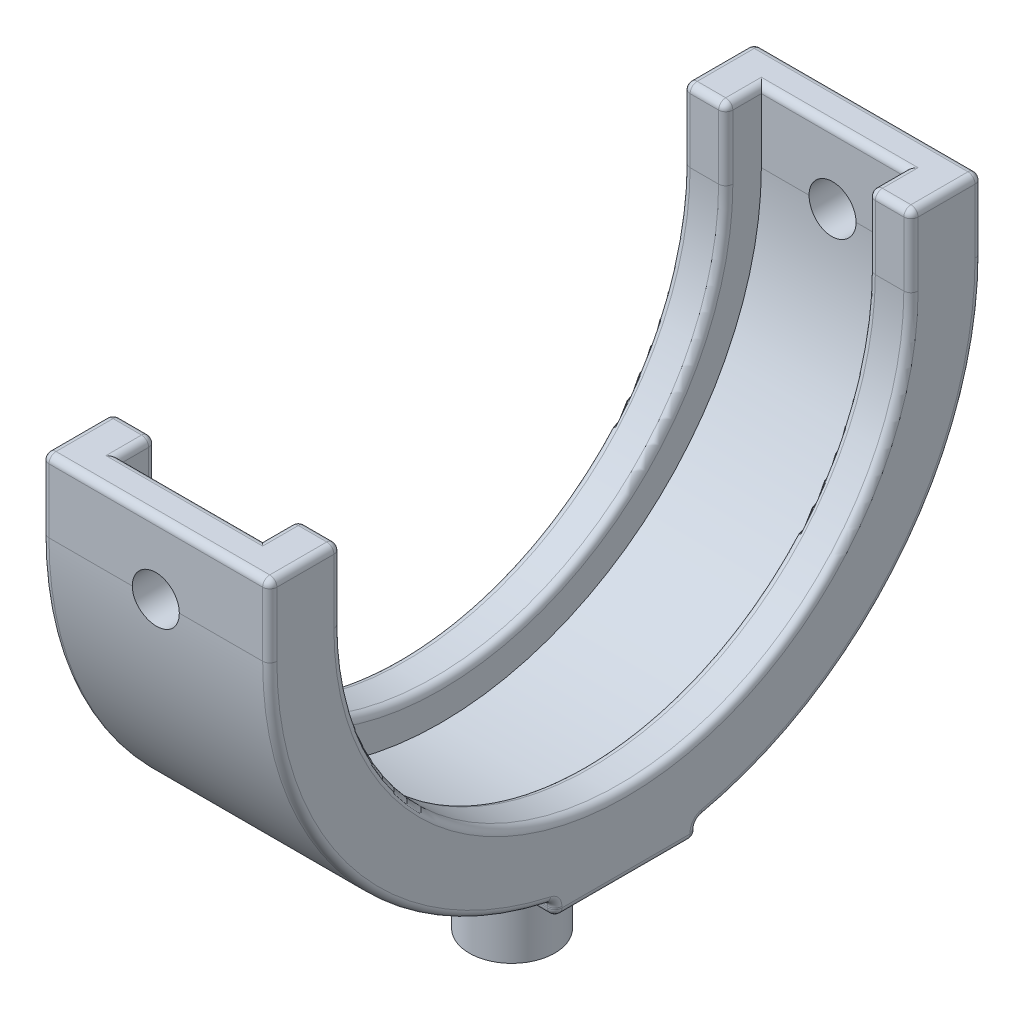
SolidWorks part; units mm, degrees
ref_plane "Front Plane" through (0, 0, 0) normal (0, 0, 1) x (1, 0, 0)
ref_plane "Top Plane" through (0, 0, 0) normal (0, 1, 0) x (1, 0, 0)
ref_plane "Right Plane" through (0, 0, 0) normal (1, 0, 0) x (0, 0, -1)
sketch "Sketch1" plane through (0, 0, 0) normal (1, 0, 0) x (0, 0, -1)
  line L0 (-25, 0) -> (25, 0)
  line L3 (-5, -24.4949) -> (-5, -25.4949)
  line L4 (-5, -25.4949) -> (5, -25.4949)
  line L5 (5, -24.4949) -> (5, -25.4949)
  arc A0 (-25, 0) -> (-5, -24.4949) centre (0, 0) ccw
  arc A1 (5, -24.4949) -> (25, 0) centre (0, 0) ccw
  point P8 (0, 0)
  dimension "D1" = 25
  dimension "D2" = 10
  dimension "D3" = 1
extrude "Boss-Extrude1" add sketch "Sketch1" along normal blind 16
sketch "Sketch2" plane through (0, 0, 0) normal (0, 1, 0) x (1, 0, 0)
  line L0 (16, -25) -> (0, -25) construction
  line L1 (3, -22.5) -> (13, -22.5)
  line L2 (3, -22.5) -> (3, -20)
  line L3 (3, 0) -> (13, 0)
  line L4 (13, -22.5) -> (13, -20)
  line L5 (16, 25) -> (16, -25) construction
  line L6 (13, -20) -> (16, -20)
  line L7 (16, 25) -> (16, -25) construction
  line L8 (13, 0) -> (16, 0)
  line L9 (16, -20) -> (16, 0)
  line L10 (8, -25) -> (8, 25) construction
  line L11 (16, 25) -> (0, 25) construction
  line L12 (3, 0) -> (0, 0)
  line L13 (0, -20) -> (0, 0)
  line L14 (3, -20) -> (0, -20)
  point P4 (8, -22.5)
  point P7 (8, -25)
  point P10 (8, 0)
  point P11 (16, 0)
  dimension "D1" = 10
  dimension "D2" = 22.5
  dimension "D3" = 5
revolve "Cut-Revolve3" cut sketch "Sketch2" angle 360 about L3
sketch "Sketch4" plane through (0, -25.4949, 0) normal (0, -1, 0) x (1, 0, 0)
  line L0 (16, 5) -> (0, 5) construction
  line L1 (0, 5) -> (0, -5) construction
  circle A0 centre (8, 0) radius 3
  point P2 (0, 0)
  point P5 (8, 5)
  point P8 (0, 0)
  point P9 (0, 0)
  dimension "D1" = 6
extrude "Boss-Extrude2" add sketch "Sketch4" along normal blind 7
sketch "Sketch18" plane through (0, 0, 0) normal (0, 1, 0) x (1, 0, 0)
  line L8 (16, -25) -> (16, -20)
  line L9 (16, -20) -> (13, -20)
  line L10 (13, -20) -> (13, -22.5)
  line L11 (13, -22.5) -> (3, -22.5)
  line L12 (3, -22.5) -> (3, -20)
  line L13 (3, -20) -> (0, -20)
  line L14 (0, -20) -> (0, -25)
  line L15 (0, -25) -> (16, -25)
  line L16 (16, -25) -> (16, -20)
  line L17 (16, -20) -> (13, -20)
  line L18 (13, -20) -> (13, -22.5)
  line L19 (13, -22.5) -> (3, -22.5)
  line L20 (3, -22.5) -> (3, -20)
  line L21 (3, -20) -> (0, -20)
  line L22 (0, -20) -> (0, -25)
  line L23 (0, -25) -> (16, -25)
  line L24 (13, 22.5) -> (13, 20)
  line L25 (13, 20) -> (16, 20)
  line L26 (16, 20) -> (16, 25)
  line L27 (16, 25) -> (0, 25)
  line L28 (0, 25) -> (0, 20)
  line L29 (0, 20) -> (3, 20)
  line L30 (3, 20) -> (3, 22.5)
  line L31 (3, 22.5) -> (13, 22.5)
  line L32 (13, 22.5) -> (13, 20)
  line L33 (13, 20) -> (16, 20)
  line L34 (16, 20) -> (16, 25)
  line L35 (16, 25) -> (0, 25)
  line L36 (0, 25) -> (0, 20)
  line L37 (0, 20) -> (3, 20)
  line L38 (3, 20) -> (3, 22.5)
  line L39 (3, 22.5) -> (13, 22.5)
  dimension "D1" = 0
  dimension "D2" = 0
extrude "Boss-Extrude3" add sketch "Sketch18" along normal blind 5
sketch "Sketch19" plane through (0, 0, 25) normal (0, 0, 1) x (1, 0, 0)
  line L0 (16, 0) -> (0, 0) construction
  circle A0 centre (8, 0) radius 1.65
  dimension "D1" = 3.3
extrude "Cut-Extrude1" cut sketch "Sketch19" against normal through all
fillet "Fillet3" radius 0.5 22 edges at (0, 5, 22.5) (1.5, 5, 20) (3, 5, 21.25) (8, 5, 22.5) (13, 5, 21.25) (14.5, 5, 20) (16, 5, 22.5) (8, 5, 25) (3, 5, -21.25) (1.5, 5, -20) (0, 5, -22.5) (8, 5, -25) (16, 5, -22.5) (14.5, 5, -20) (13, 5, -21.25) (8, 5, -22.5) (16, -25.4949, 0) (0, -25.4949, 0) (8, -24.4949, 5) (8, -25.4949, 5) (8, -25.4949, -5) (8, -24.4949, -5)
fillet "Fillet5" radius 0.5 20 edges at (15.8536, 4.8536, 20.1464) (15.8536, 4.8536, -20.1464) (0.1464, 4.8536, 20.1464) (0.1464, 4.8536, -20.1464) (13.1464, 4.8536, -20.1464) (13.1464, 4.8536, 20.1464) (2.8536, 4.8536, 20.1464) (2.8536, 4.8536, -20.1464) (16, 2.25, -20) (16, -20, 0) (16, 2.25, 20) (0, 2.25, -20) (0, -20, 0) (0, 2.25, 20) (13, 2.25, 20) (13, -20, 0) (13, 2.25, -20) (3, 2.25, -20) (3, -20, 0) (3, 2.25, 20)
fillet "Fillet6" radius 0.5 24 edges at (0.1464, -25.3485, -4.8536) (0.1464, 4.8536, -24.8536) (0.1464, 4.8536, 24.8536) (0.1464, -25.3485, 4.8536) (15.8536, 4.8536, 24.8536) (15.8536, -25.3485, 4.8536) (15.8536, -25.3485, -4.8536) (15.8536, 4.8536, -24.8536) (0, 2.25, -25) (0, -15.6556, -19.4911) (16, -24.9473, -5) (0, -24.5867, -5.1102) (0, -24.9473, -5) (0, -24.9473, 5) (16, -24.9473, 5) (0, -24.5867, 5.1102) (0, -15.6556, 19.4911) (0, 2.25, 25) (16, 2.25, 25) (16, -15.6556, 19.4911) (16, -24.5867, 5.1102) (16, -24.5867, -5.1102) (16, 2.25, -25) (16, -15.6556, -19.4911)
